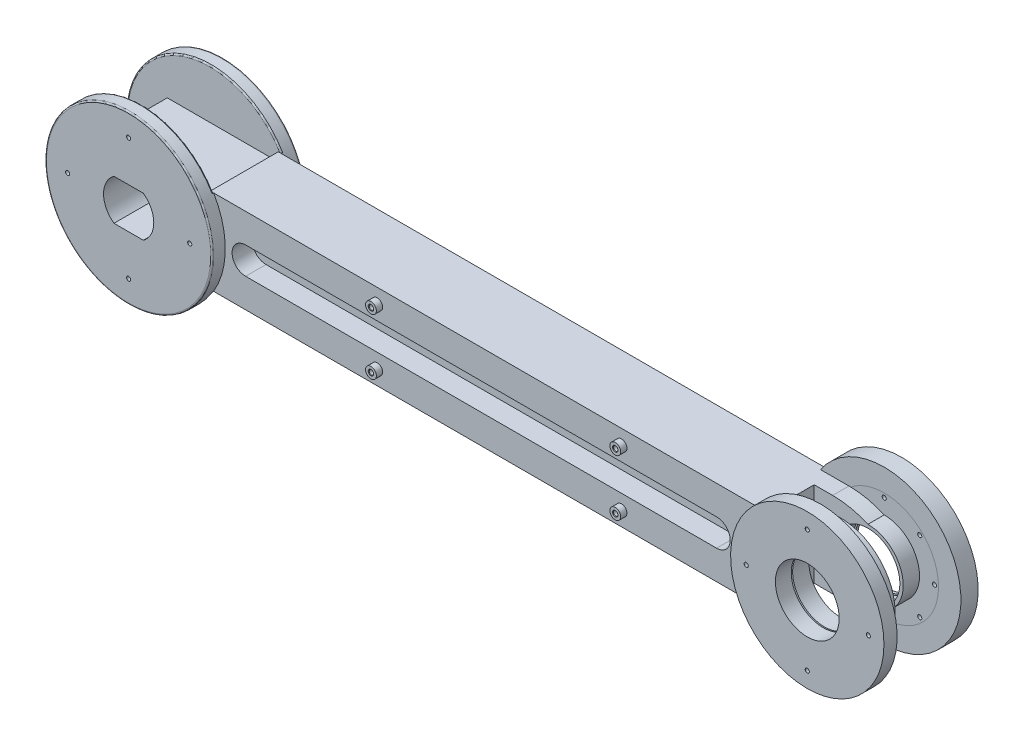
SolidWorks part; units mm, degrees
ref_plane "Front Plane" through (0, 0, 0) normal (0, 0, 1) x (1, 0, 0)
ref_plane "Top Plane" through (0, 0, 0) normal (0, 1, 0) x (1, 0, 0)
ref_plane "Right Plane" through (0, 0, 0) normal (1, 0, 0) x (0, 0, -1)
sketch "Sketch1" plane through (0, 0, 0) normal (0, 0, 1) x (1, 0, 0)
  line L0 (0, 0) -> (500, 0) construction
  line L1 (50.5105, 31.4285) -> (250, 31.4285)
  line L2 (250, 0) -> (250, 88.1142) construction
  line L4 (250, 31.4285) -> (474, 31.4285)
  line L5 (250, -31.4285) -> (474, -31.4285)
  line L6 (50.5105, -31.4285) -> (250, -31.4285)
  arc A0 (10.877, 38.4927) -> (10.877, -38.4927) centre (0, 0) ccw
  arc A2 (10.877, 38.4927) -> (50.5105, 31.4285) centre (48.5222, 134.9863) ccw
  arc A5 (10.877, -38.4927) -> (50.5105, -31.4285) centre (48.5222, -134.9863) cw
  arc A6 (500, -26) -> (500, 26) centre (500, 0) ccw
  arc A7 (474, 31.4285) -> (500, 26) centre (474, -33.5494) cw
  arc A8 (474, -31.4285) -> (500, -26) centre (474, 33.5494) ccw
  dimension "D1" = 80
  dimension "D4" = 52
  dimension "D3" = 500
extrude "Boss-Extrude1" add sketch "Sketch1" along normal blind 50
sketch "Sketch3" plane through (0, 0, 50) normal (0, 0, 1) x (1, 0, 0)
  line L0 (0, 0) -> (65.144, 0) construction
  line L1 (10.8282, 15) -> (-10.8282, 15)
  line L2 (10.8282, -15) -> (-10.8282, -15)
  circle A0 centre (0, 0) radius 18.5
  dimension "D1" = 37
  dimension "D2" = 15
extrude "Cut-Extrude1" cut sketch "Sketch3" against normal blind 54
sketch "Sketch4" plane through (0, 0, 50) normal (0, 0, 1) x (1, 0, 0)
  line L0 (0, 0) -> (500, 0) construction
  line L1 (419.6946, -9.2477) -> (250, 0) construction
  line L2 (423.5, -10) -> (76.5, -10)
  line L4 (423.5, 10) -> (76.5, 10)
  line L8 (419.6946, 9.2477) -> (80.3054, -9.2477) construction
  arc A0 (76.5, 10) -> (76.5, -10) centre (76.5, 0) ccw
  arc A2 (423.5, -10) -> (423.5, 10) centre (423.5, 0) ccw
  point P4 (250, 0)
extrude "Cut-Extrude2" cut sketch "Sketch4" against normal blind 15
sketch "Sketch5" plane through (0, 0, 0) normal (0, 0, -1) x (-1, 0, 0)
  line L2 (-423.5, -10) -> (-76.5, -10)
  line L3 (-76.5, 10) -> (-423.5, 10)
  line L4 (-423.5, -10) -> (-76.5, -10)
  line L5 (-76.5, 10) -> (-423.5, 10)
  arc A2 (-76.5, -10) -> (-76.5, 10) centre (-76.5, 0) ccw
  arc A3 (-423.5, 10) -> (-423.5, -10) centre (-423.5, 0) ccw
  arc A4 (-76.5, -10) -> (-76.5, 10) centre (-76.5, 0) ccw
  arc A5 (-423.5, 10) -> (-423.5, -10) centre (-423.5, 0) ccw
  dimension "D1" = 0
extrude "Cut-Extrude3" cut sketch "Sketch5" against normal blind 15
sketch "Sketch6" plane through (0, 0, 0) normal (0, 1, 0) x (1, 0, 0)
  line L0 (540, -25) -> (329.6151, -25) construction
  line L7 (619.621, -35) -> (460.379, -35)
  line L8 (619.621, -35) -> (619.621, -15)
  line L9 (619.621, -15) -> (460.379, -15)
  line L10 (460.379, -35) -> (460.379, -15)
  line L11 (619.621, -35) -> (460.379, -15) construction
  line L12 (619.621, -15) -> (460.379, -35) construction
  dimension "D1" = 20
extrude "Cut-Extrude4" cut sketch "Sketch6" against normal mid plane 200
sketch "Sketch7" plane through (0, 0, 50) normal (0, 0, 1) x (1, 0, 0)
  circle A0 centre (500, 0) radius 23.5
  dimension "D1" = 47
extrude "Cut-Extrude5" cut sketch "Sketch7" against normal mid plane 200
sketch "Sketch8" plane through (0, 0, 50) normal (0, 0, 1) x (1, 0, 0)
  circle A0 centre (500, 0) radius 25
  dimension "D1" = 50
extrude "Cut-Extrude6" cut sketch "Sketch8" against normal mid plane 1 from offset 2 offset against normal yes
sketch "Sketch12" plane through (0, 0, 0) normal (0, 0, -1) x (-1, 0, 0)
  circle A0 centre (-500, 0) radius 40
  circle A1 centre (-500, 0) radius 26
  dimension "D1" = 80
extrude "Boss-Extrude3" add sketch "Sketch12" against normal blind 3
sketch "Sketch13" plane through (0, 0, 50) normal (0, 0, 1) x (1, 0, 0)
  line L0 (335.1904, 0) -> (584.0246, 0) construction
  line L1 (460.379, 31.4285) -> (460.379, -31.4285)
  arc A0 (483.665, -36.5126) -> (483.665, 36.5126) centre (500, 0) ccw
  arc A1 (460.379, 31.4285) -> (483.665, 36.5126) centre (454.482, 114.3075) ccw
  arc A2 (460.379, -31.4285) -> (483.665, -36.5126) centre (454.482, -114.3075) cw
  circle A3 centre (500, 0) radius 23.5
extrude "Boss-Extrude4" add sketch "Sketch13" against normal blind 15
sketch "Sketch10" plane through (0, 0, 0) normal (0, 0, -1) x (-1, 0, 0)
  line L0 (-500, 0) -> (-500, 64.6626) construction
  circle A0 centre (-500, 0) radius 37 construction
  circle A1 centre (-500, 37) radius 1.525
  circle A5 centre (-500, -37) radius 1.525
  circle A6 centre (-526.163, -26.163) radius 1.525
  circle A7 centre (-537, 0) radius 1.525
  circle A8 centre (-526.163, 26.163) radius 1.525
  circle A9 centre (-473.837, 26.163) radius 1.525 [skipped]
  circle A10 centre (-463, 0) radius 1.525 [skipped]
  circle A11 centre (-473.837, -26.163) radius 1.525 [skipped]
  point P23 (-500, 0)
  dimension "D1" = 74
  dimension "D2" = 3.05
  dimension "D3" = 8
extrude "Cut-Extrude7" cut sketch "Sketch10" against normal mid plane 38
sketch "Sketch14" plane through (0, 0, 50) normal (0, 0, 1) x (1, 0, 0)
  circle A0 centre (500, 0) radius 25
  dimension "D1" = 50
extrude "Cut-Extrude8" cut sketch "Sketch14" against normal blind 1 from offset 2 offset against normal yes
sketch "Sketch15" plane through (0, 0, 0) normal (0, 0, -1) x (-1, 0, 0)
  circle A0 centre (-500, 0) radius 22.5
  circle A1 centre (-500, 0) radius 23.5
  dimension "D1" = 45
  dimension "D2" = 47
extrude "Boss-Extrude5" add sketch "Sketch15" against normal blind 2
sketch "Sketch16" plane through (0, 0, 50) normal (0, 0, 1) x (1, 0, 0)
  line L0 (10.8282, -15) -> (-10.8282, -15) construction
  line L1 (26, 55.7337) -> (26, -55.7337) construction
  line L2 (10.8282, 15) -> (-10.8282, 15) construction
  line L3 (10.8282, -15) -> (-10.8282, -15)
  line L6 (0, 0) -> (0, 87.0116) construction
  line L7 (10.8282, 15) -> (-10.8282, 15)
  circle A0 centre (0, 0) radius 61.5
  arc A2 (10.8282, -15) -> (10.8282, 15) centre (0, 0) ccw construction
  arc A3 (-10.8282, 15) -> (-10.8282, -15) centre (0, 0) ccw construction
  arc A4 (10.8282, -15) -> (10.8282, 15) centre (0, 0) ccw
  arc A5 (-10.8282, 15) -> (-10.8282, -15) centre (0, 0) ccw
  circle A18 centre (500, 0) radius 56.5
  circle A19 centre (500, 0) radius 23.5
  dimension "D2" = 123
  dimension "D3" = 47
  dimension "D1" = 113
  dimension "D4" = 26
extrude "Boss-Extrude8" add sketch "Sketch16" along normal blind 9.7
sketch "Sketch22" plane through (0, 0, 0) normal (0, 0, 1) x (1, 0, 0)
  line L1 (26, 55.7337) -> (26, -55.7337) construction
  line L3 (10.8282, -15) -> (-10.8282, -15)
  line L6 (0, 0) -> (0, 87.0116) construction
  line L7 (10.8282, 15) -> (-10.8282, 15)
  circle A0 centre (0, 0) radius 61.5
  arc A4 (10.8282, -15) -> (10.8282, 15) centre (0, 0) ccw
  arc A5 (-10.8282, 15) -> (-10.8282, -15) centre (0, 0) ccw
  dimension "D2" = 123
  dimension "D4" = 26
extrude "Boss-Extrude9" add sketch "Sketch22" against normal blind 9.7
hole_wizard "M3 Tapped Hole1" positions "Sketch19" profile "Sketch20" tap size "M3" standard "ISO"
sketch "Sketch19" plane through (0, 0, 59.7) normal (0, 0, 1) x (1, 0, 0)
  point P0 (500, 45)
  point P3 (545, 0)
  point P6 (455, 0)
  point P9 (500, -45)
  point P12 (-45, 0)
  point P15 (0, 45)
  point P18 (45, 0)
  point P21 (0, -45)
sketch "Sketch20" plane through (500, 45, 59.7) normal (1, 0, 0) x (0, -1, 0)
  line L0 (0, 0) -> (0, 7.5)
  line L1 (0, 7.5) -> (1.25, 6.7489)
  line L2 (1.25, 6.7489) -> (1.25, 6)
  line L3 (1.25, 6) -> (1.5, 6)
  line L5 (1.5, 6) -> (1.5, 0.025)
  line L6 (1.5, 0.025) -> (1.525, 0)
  line L7 (1.525, 0) -> (0, 0)
  line L8 (-1.5, 0.025) -> (-1.525, 0) construction
  line L10 (0, 7.5) -> (-1.25, 6.7489) construction
  line L11 (0, -6.35) -> (0, 107.95) construction
  dimension "Tap Drill Dia." = 2.5
  dimension "Tap Drill Depth" = 7.5
  dimension "Thread Major Dia." = 3
  dimension "Thread Depth" = 6
  dimension "Near C'Sink Dia." = 3.05
  dimension "Near C'Sink Angle" = 90
  dimension "Drill Angle" = 118
hole_wizard "M3 Tapped Hole2" positions "Sketch23" profile "Sketch24" tap size "M3" standard "ISO"
sketch "Sketch23" plane through (0, 0, -9.7) normal (0, 0, -1) x (-1, 0, 0)
  point P0 (0, 45)
  point P3 (45, 0)
  point P6 (0, -45)
  point P9 (-45, 0)
sketch "Sketch24" plane through (0, 45, -9.7) normal (1, 0, 0) x (0, 1, 0)
  line L0 (0, 0) -> (0, 8.2511)
  line L1 (0, 8.2511) -> (1.25, 7.5)
  line L2 (1.25, 7.5) -> (1.25, 6)
  line L3 (1.25, 6) -> (1.5, 6)
  line L5 (1.5, 6) -> (1.5, 0.025)
  line L6 (1.5, 0.025) -> (1.525, 0)
  line L7 (1.525, 0) -> (0, 0)
  line L8 (-1.5, 0.025) -> (-1.525, 0) construction
  line L10 (0, 8.2511) -> (-1.25, 7.5) construction
  line L11 (0, -6.35) -> (0, 107.95) construction
  dimension "Tap Drill Dia." = 2.5
  dimension "Tap Drill Depth" = 7.5
  dimension "Thread Major Dia." = 3
  dimension "Thread Depth" = 6
  dimension "Near C'Sink Dia." = 3.05
  dimension "Near C'Sink Angle" = 90
  dimension "Drill Angle" = 118
sketch "Sketch25" plane through (0, 0, 0) normal (0, 0, -1) x (-1, 0, 0)
  line L0 (-475.2413, 31.4167) -> (-460.379, 31.4285)
  line L1 (-475.2413, -31.4167) -> (-460.379, -31.4285)
  line L2 (-460.379, 31.4285) -> (-453.0479, 31.4285)
  line L3 (-453.0479, -31.4285) -> (-460.379, -31.4285)
  line L4 (-460.379, 31.4285) -> (-453.0479, 31.4285)
  line L5 (-453.0479, -31.4285) -> (-460.379, -31.4285)
  arc A0 (-475.2413, 31.4167) -> (-475.2413, -31.4167) centre (-500, 0) ccw construction
  arc A1 (-475.2413, 31.4167) -> (-475.2413, -31.4167) centre (-500, 0) ccw
  arc A4 (-483.665, 36.5126) -> (-460.379, 31.4285) centre (-454.482, 114.3075) ccw
  arc A5 (-453.0479, 31.4285) -> (-453.0479, -31.4285) centre (-500, 0) ccw
  arc A6 (-460.379, -31.4285) -> (-483.665, -36.5126) centre (-454.482, -114.3075) ccw
  arc A7 (-483.665, 36.5126) -> (-483.665, -36.5126) centre (-500, 0) ccw
  arc A8 (-483.665, 36.5126) -> (-460.379, 31.4285) centre (-454.482, 114.3075) ccw
  arc A9 (-453.0479, 31.4285) -> (-453.0479, -31.4285) centre (-500, 0) ccw
  arc A10 (-460.379, -31.4285) -> (-483.665, -36.5126) centre (-454.482, -114.3075) ccw
  arc A11 (-483.665, 36.5126) -> (-483.665, -36.5126) centre (-500, 0) ccw
  line M12 (-474, -31.4285) -> (-52.863, -31.4285)
  line M14 (-52.863, 31.4285) -> (-474, 31.4285)
  arc M15 (-474, 31.4285) -> (-475.2413, 31.4167) centre (-474, -33.5494) ccw
  arc M16 (-475.2413, 31.4167) -> (-475.2413, -31.4167) centre (-500, 0) ccw
  arc M17 (-475.2413, -31.4167) -> (-474, -31.4285) centre (-474, 33.5494) ccw
  dimension "D1" = 0
extrude "Boss-Extrude10" add sketch "Sketch25" along normal blind 9.7 and the other way up to surface (3 mm away) separate body contours A10 A1 A8 A9 M12 M14 | A8 M16 M15 M14 | A10 M12 M17 M16 other way up to face at (498.475, 37, 3)
hole_wizard "M3 Tapped Hole3" positions "Sketch26" profile "Sketch27" tap size "M3" standard "ISO"
sketch "Sketch26" plane through (0, 0, -9.7) normal (0, 0, -1) x (-1, 0, 0)
  point P0 (-500, 45)
  point P3 (-545, 0)
  point P6 (-500, -45)
  point P9 (-455, 0)
sketch "Sketch27" plane through (500, 45, -9.7) normal (1, 0, 0) x (0, 1, 0)
  line L0 (0, 0) -> (0, 8.2511)
  line L1 (0, 8.2511) -> (1.25, 7.5)
  line L2 (1.25, 7.5) -> (1.25, 6)
  line L3 (1.25, 6) -> (1.5, 6)
  line L5 (1.5, 6) -> (1.5, 0.025)
  line L6 (1.5, 0.025) -> (1.525, 0)
  line L7 (1.525, 0) -> (0, 0)
  line L8 (-1.5, 0.025) -> (-1.525, 0) construction
  line L10 (0, 8.2511) -> (-1.25, 7.5) construction
  line L11 (0, -6.35) -> (0, 107.95) construction
  dimension "Tap Drill Dia." = 2.5
  dimension "Tap Drill Depth" = 7.5
  dimension "Thread Major Dia." = 3
  dimension "Thread Depth" = 6
  dimension "Near C'Sink Dia." = 3.05
  dimension "Near C'Sink Angle" = 90
  dimension "Drill Angle" = 118
fillet "Fillet1" radius 1 4 edges at (61.5, 0, 59.7) (-61.5, 0, 50) (-61.5, 0, 0) (61.5, 0, -9.7)
sketch "Sketch28" plane through (0, 15, 0) normal (0, -1, 0) x (1, 0, 0)
  circle A0 centre (0, 25) radius 1.525
  dimension "D1" = 3.05
extrude "Cut-Extrude9" cut sketch "Sketch28" against normal blind 27
sketch "Sketch29" plane through (0, 15, 0) normal (0, -1, 0) x (1, 0, 0)
  line L0 (10.877, 50) -> (50.5105, 50) construction
  line L1 (50.5105, 0) -> (10.877, 0) construction
  line L2 (50.5105, 50) -> (50.5105, 0) construction
  line L8 (-40.2752, 50) -> (-40.2752, 0)
  line L9 (-40.2752, 0) -> (50.5105, 0)
  line L10 (50.5105, 0) -> (50.5105, 50)
  line L11 (50.5105, 50) -> (-40.2752, 50)
extrude "Cut-Extrude10" cut sketch "Sketch29" against normal blind 29 from offset 10 offset against normal yes
sketch "Sketch30" plane through (0, 0, 0) normal (0, 0, -1) x (-1, 0, 0)
  line L0 (-263.4315, 31.4285) -> (-263.4315, -138.0898) construction
  line L1 (-474, 31.4285) -> (-52.863, 31.4285) construction
  line L2 (-353.4315, 31.4285) -> (-353.4315, 10) construction
  line L3 (-76.5, 10) -> (-423.5, 10) construction
  line L4 (-353.4315, 20.7143) -> (-263.4315, 20.7143) construction
  line L5 (-433.5, 0) -> (140.0242, 0) construction
  circle A0 centre (-353.4315, 20.7143) radius 4
  circle A1 centre (-173.4315, 20.7143) radius 4
  arc A2 (-423.5, 10) -> (-423.5, -10) centre (-423.5, 0) ccw construction
  circle A3 centre (-173.4315, -20.7143) radius 4
  circle A4 centre (-353.4315, -20.7143) radius 4
  dimension "D2" = 8
  dimension "D1" = 90
extrude "Boss-Extrude11" add sketch "Sketch30" along normal blind 4.6
ref_plane "Plane1" through (0, 0, 25) normal (0, 0, -1) x (-1, 0, 0)
mirror "Mirror1" about plane through (0, 0, 25) normal (0, 0, -1) of "Boss-Extrude11"
hole_wizard "M4 Tapped Hole1" positions "Sketch31" profile "Sketch32" tap size "M4" standard "ISO"
sketch "Sketch31" plane through (0, 0, -4.6) normal (0, 0, -1) x (-1, 0, 0)
  point P0 (-353.4315, 20.7143)
  point P4 (-353.4315, -20.7143)
  point P7 (-173.4315, -20.7143)
  point P10 (-173.4315, 20.7143)
sketch "Sketch32" plane through (353.4315, 20.7143, -4.6) normal (1, 0, 0) x (0, 1, 0)
  line L0 (0, 0) -> (0, 12.4914)
  line L1 (0, 12.4914) -> (1.65, 11.5)
  line L2 (1.65, 11.5) -> (1.65, 0.375)
  line L3 (1.65, 0.375) -> (2.025, 0)
  line L5 (2.025, 0) -> (0, 0)
  line L6 (-1.65, 0.375) -> (-2.025, 0) construction
  line L10 (0, 12.4914) -> (-1.65, 11.5) construction
  line L11 (0, -6.35) -> (0, 107.95) construction
  dimension "Tap Drill Dia." = 3.3
  dimension "Tap Drill Depth" = 11.5
  dimension "Near C'Sink Dia." = 4.05
  dimension "Near C'Sink Angle" = 90
  dimension "Drill Angle" = 118
cosmetic thread "Hole Thread16" parameters "D1"=8, "D2"=4
cosmetic thread "Hole Thread17" parameters "D1"=8, "D2"=4
cosmetic thread "Hole Thread18" parameters "D1"=8, "D2"=4
cosmetic thread "Hole Thread19" parameters "D1"=8, "D2"=4
hole_wizard "M4 Tapped Hole2" positions "Sketch33" profile "Sketch34" tap size "M4" standard "ISO"
sketch "Sketch33" plane through (0, 0, 54.6) normal (0, 0, 1) x (1, 0, 0)
  point P0 (173.4315, 20.7143)
  point P3 (173.4315, -20.7143)
  point P6 (353.4315, -20.7143)
  point P9 (353.4315, 20.7143)
sketch "Sketch34" plane through (173.4315, 20.7143, 54.6) normal (1, 0, 0) x (0, -1, 0)
  line L0 (0, 0) -> (0, 12.4914)
  line L1 (0, 12.4914) -> (1.65, 11.5)
  line L2 (1.65, 11.5) -> (1.65, 0.375)
  line L3 (1.65, 0.375) -> (2.025, 0)
  line L5 (2.025, 0) -> (0, 0)
  line L6 (-1.65, 0.375) -> (-2.025, 0) construction
  line L10 (0, 12.4914) -> (-1.65, 11.5) construction
  line L11 (0, -6.35) -> (0, 107.95) construction
  dimension "Tap Drill Dia." = 3.3
  dimension "Tap Drill Depth" = 11.5
  dimension "Near C'Sink Dia." = 4.05
  dimension "Near C'Sink Angle" = 90
  dimension "Drill Angle" = 118
cosmetic thread "Hole Thread20" parameters "D1"=8, "D2"=4
cosmetic thread "Hole Thread21" parameters "D1"=8, "D2"=4
cosmetic thread "Hole Thread22" parameters "D1"=8, "D2"=4
cosmetic thread "Hole Thread23" parameters "D1"=8, "D2"=4
